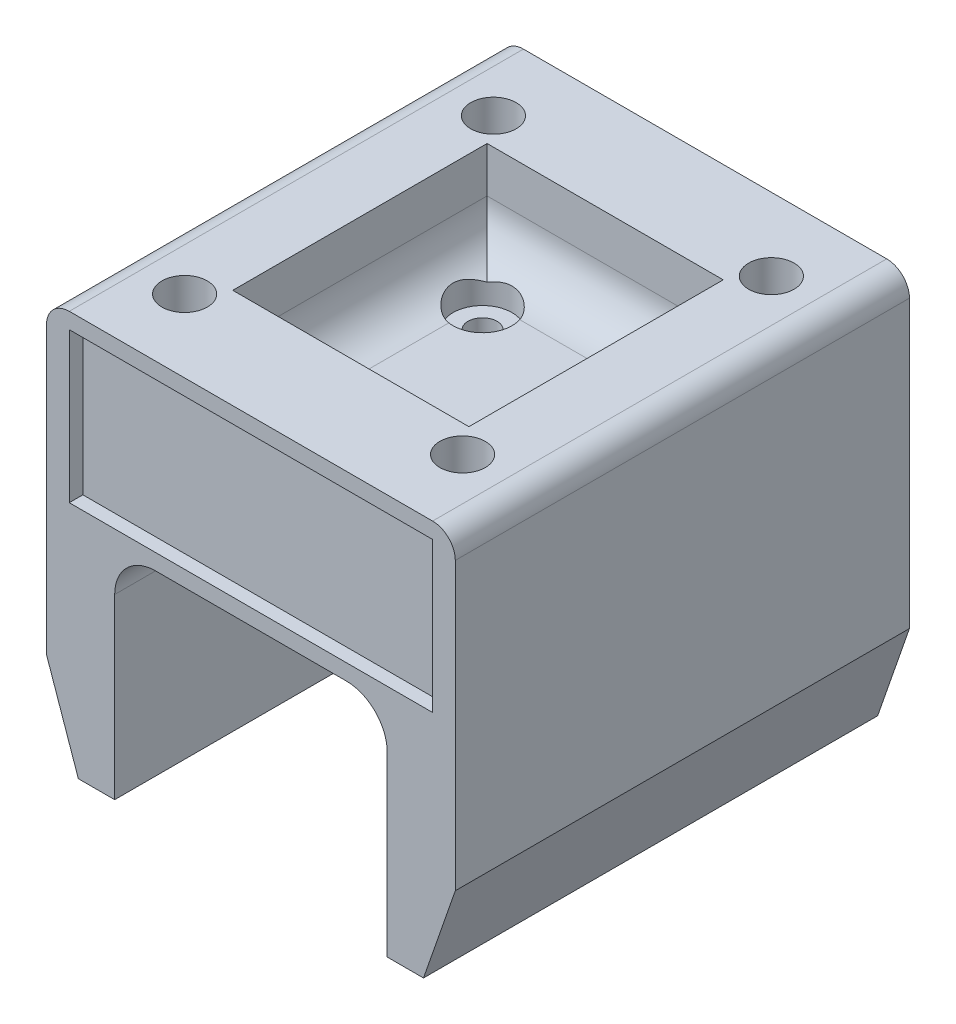
SolidWorks part; units mm, degrees
material "ABS"
ref_plane "Alzado" through (0, 0, 0) normal (0, 0, 1) x (1, 0, 0)
ref_plane "Planta" through (0, 0, 0) normal (0, 1, 0) x (1, 0, 0)
ref_plane "Vista lateral" through (0, 0, 0) normal (1, 0, 0) x (0, 0, -1)
sketch "Sketch1" plane through (0, 0, 0) normal (0, 1, 0) x (1, 0, 0)
  line L1 (-22.5, -25) -> (22.5, -25)
  line L2 (-22.5, -25) -> (-22.5, 25)
  line L3 (-22.5, 25) -> (22.5, 25)
  line L4 (22.5, -25) -> (22.5, 25)
  line L5 (-22.5, -25) -> (22.5, 25) construction
  line L6 (-22.5, 25) -> (22.5, -25) construction
  line L7 (-7.5, -8) -> (7.5, -8) construction
  line L8 (-7.5, -8) -> (-7.5, 8) construction
  line L9 (-7.5, 8) -> (7.5, 8) construction
  line L10 (7.5, -8) -> (7.5, 8) construction
  line L11 (-7.5, -8) -> (7.5, 8) construction
  line L12 (-7.5, 8) -> (7.5, -8) construction
  circle A0 centre (-7.5, 8) radius 1.5
  circle A1 centre (7.5, 8) radius 1.5
  circle A2 centre (7.5, -8) radius 1.5
  circle A3 centre (-7.5, -8) radius 1.5
  circle A4 centre (15.3, 17) radius 2.5
  circle A5 centre (-15.3, 17) radius 2.5
  circle A6 centre (-15.3, -17) radius 2.5
  circle A7 centre (15.3, -17) radius 2.5
  point P0 (0, 0)
  point P6 (0, 0)
  point P23 (0, 0)
  point P24 (0, 0)
  point P25 (0, 0)
  point P26 (0, 0)
  dimension "D5" = 3
  dimension "D7" = 5
  dimension "D1" = 45
  dimension "D2" = 50
  dimension "D3" = 16
  dimension "D4" = 15
  dimension "D6" = 34
  dimension "D8" = 17
extrude "Boss-Extrude1" add sketch "Sketch1" along normal blind 20
sketch "Sketch3" plane through (0, 20, 0) normal (0, 1, 0) x (1, 0, 0)
  line L1 (-13, -14) -> (13, -14)
  line L2 (-13, -14) -> (-13, 14)
  line L3 (-13, 14) -> (13, 14)
  line L4 (13, -14) -> (13, 14)
  line L5 (-13, -14) -> (13, 14) construction
  line L6 (-13, 14) -> (13, -14) construction
  point P0 (0, 0)
  dimension "D1" = 28
  dimension "D2" = 26
extrude "Cut-Extrude1" cut sketch "Sketch3" against normal blind 10
sketch "Sketch7" plane through (0, 10, 0) normal (0, 1, 0) x (1, 0, 0)
  point P0 (-7.5, 8)
  point P3 (-7.5, -8)
  point P6 (7.5, -8)
  point P9 (7.5, 8)
hole_wizard "Refrentado para tornillo con cabeza plana de M32" positions "Sketch7" profile "Sketch8" counterbore size "M3" standard "ISO" end condition through all
sketch "Sketch8" plane through (-7.5, 10, -8) normal (1, 0, 0) x (0, 0, 1)
  line L0 (0, 0) -> (0, 10)
  line L1 (0, 10) -> (1.6, 10)
  line L3 (1.6, 10) -> (1.6, 2)
  line L4 (1.6, 2) -> (3.25, 2)
  line L5 (3.25, 2) -> (3.25, 0)
  line L7 (3.25, 0) -> (0, 0)
  line L11 (0, -6.35) -> (0, 107.95) construction
  dimension "Diámetro de taladro hasta el siguiente" = 3.2
  dimension "Profundidad de taladro hasta el siguiente" = 10
  dimension "Diámetro de refrentado" = 6.5
  dimension "Profundidad de refrentado" = 2
fillet "Fillet4" radius 5 4 edges at (0, 10, 14) (13, 10, 0) (0, 10, -14) (-13, 10, 0)
sketch "Sketch4" plane through (0, 10, 0) normal (0, 1, 0) x (1, 0, 0)
sketch "Sketch9" plane through (0, 0, 25) normal (0, 0, 1) x (1, 0, 0)
  line L0 (-1020, 10) -> (48980, 10) construction
  line L1 (-22.5, 20) -> (-22.5, 0) construction
  line L3 (-20, 1.75) -> (20, 1.75)
  line L4 (-20, 1.75) -> (-20, 18.25)
  line L5 (-20, 18.25) -> (20, 18.25)
  line L6 (20, 1.75) -> (20, 18.25)
  line L7 (-20, 1.75) -> (20, 18.25) construction
  line L8 (-20, 18.25) -> (20, 1.75) construction
  point P1 (0, 10)
  point P5 (-22.5, 10)
  dimension "D1" = 40
  dimension "D2" = 16.5
extrude "Cut-Extrude2" cut sketch "Sketch9" against normal blind 1.5
sketch "Sketch10" plane through (0, 0, -25) normal (0, 0, -1) x (-1, 0, 0)
  line L15 (-15, 0) -> (-15, -24.0677)
  line L16 (-22.5, 0) -> (22.5, 0) construction
  line L17 (-15, -24.0677) -> (-19, -24.0677)
  line L19 (-19, -24.0677) -> (-22.5, -14)
  line L21 (-22.5, -14) -> (-22.5, 0)
  line L22 (-22.5, 0) -> (-15, 0)
  dimension "D1" = 15
  dimension "D2" = 14
  dimension "D3" = 4
extrude "Boss-Extrude4" add sketch "Sketch10" against normal through all
mirror "Mirror1" about plane through (0, 0, 0) normal (1, 0, 0) of "Boss-Extrude4"
fillet "Fillet5" radius 4.5 2 edges at (15, 0, 0) (-15, 0, 0)
fillet "Fillet6" radius 2.5 2 edges at (22.5, 20, 0) (-22.5, 20, 0)
